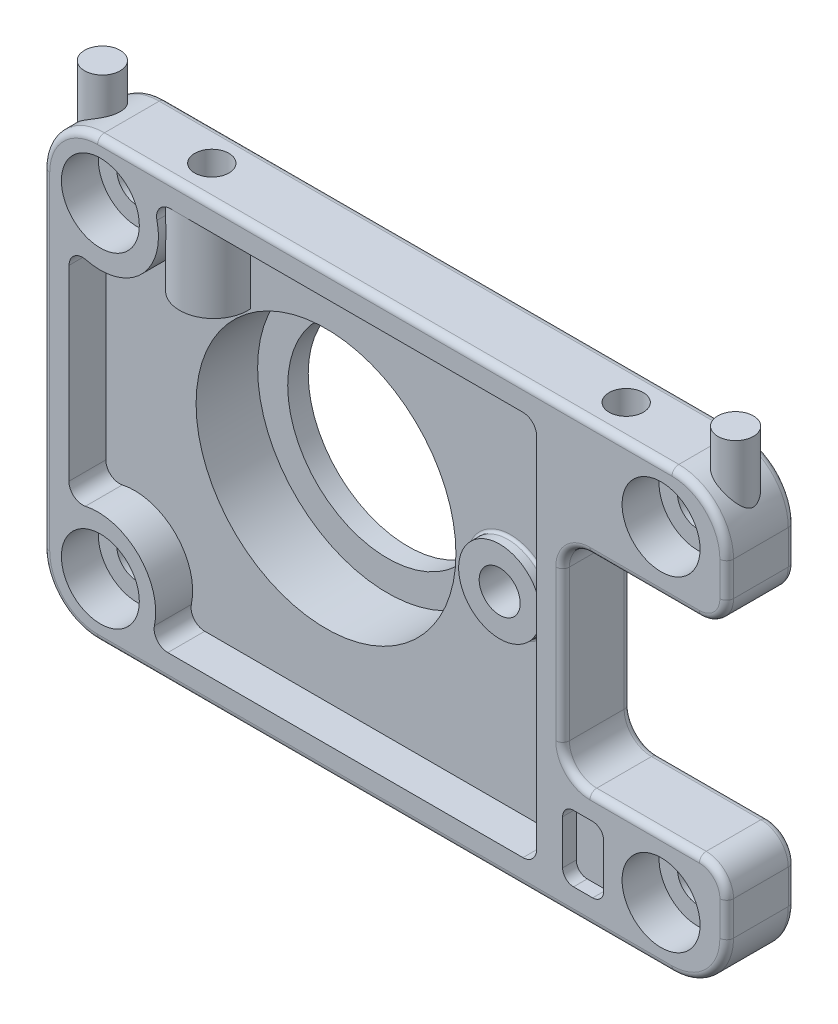
SolidWorks part; units mm, degrees
note: The reader was unsure of these and kept them because the rebuilt part matched: shared geometry of "草图15<3>", "草图16<2>", "草图16<3>".
ref_plane "前视基准面" through (0, 0, 0) normal (0, 0, 1) x (1, 0, 0)
ref_plane "上视基准面" through (0, 0, 0) normal (0, 1, 0) x (1, 0, 0)
ref_plane "右视基准面" through (0, 0, 0) normal (1, 0, 0) x (0, 0, -1)
sketch "草图1" plane through (0, 0, 0) normal (0, 0, 1) x (1, 0, 0)
  line L0 (0, 16) -> (50, 16) construction
  line L1 (0, 0) -> (50, 0)
  line L2 (0, 0) -> (0, 32)
  line L3 (0, 32) -> (50, 32)
  line L4 (50, 0) -> (50, 8.5)
  line L5 (50, 23.5) -> (38, 23.5)
  line L6 (38, 23.5) -> (38, 8.5)
  line L7 (50, 8.5) -> (38, 8.5)
  line L8 (50, 23.5) -> (50, 32)
  line L9 (4.2, 27.9) -> (5.7, 27.9) construction
  line L10 (4.2, 27.9) -> (46.7, 27.9) construction
  line L11 (4.2, 4.1) -> (50, 4.25) construction
  line L12 (25, 0) -> (25, 37.6238) construction
  circle A0 centre (4.2, 27.9) radius 1.5
  circle A1 centre (45.2, 27.9) radius 1.5
  circle A2 centre (45.2, 4.1) radius 1.5
  circle A3 centre (4.2, 4.1) radius 1.5
  circle A4 centre (18, 16) radius 9.5
  point P22 (38, 16)
  dimension "D3" = 3
  dimension "D10" = 18
  dimension "D11" = 19
  dimension "D1" = 50
  dimension "D2" = 32
  dimension "D6" = 4.2
  dimension "D8" = 23.8
  dimension "D12" = 8.5
  dimension "D13" = 12
  dimension "D14" = 41
  dimension "D4" = 2
  dimension "D5" = 2
extrude "凸台-拉伸1" add sketch "草图1" along normal blind 5
sketch "草图2" plane through (0, 0, 5) normal (0, 0, 1) x (1, 0, 0)
  line L0 (38, 8.5) -> (38, 23.5) construction
  line L1 (38, 25.2613) -> (41, 25.2613)
  line L2 (38, 25.2613) -> (38, 30.1)
  line L3 (36.1, 1.9) -> (36.1, 30.1)
  line L4 (7.6949, 1.9) -> (36.1, 1.9)
  line L5 (36.1, 30.1) -> (7.8363, 30.1)
  line L6 (38, 30.1) -> (41, 30.1)
  line L7 (41, 25.2613) -> (41, 30.1)
  line L8 (38, 6.74) -> (38, 1.9)
  line L9 (38, 1.9) -> (41, 1.9)
  line L10 (41, 1.9) -> (41, 6.74)
  line L11 (41, 6.74) -> (38, 6.74)
  line L24 (1.9124, 24.3182) -> (1.9, 7.6949)
  circle A0 centre (4.2, 27.9) radius 1.5 construction
  circle A1 centre (4.2, 27.9) radius 1.5 construction
  circle A2 centre (4.2, 4.1) radius 1.5 construction
  circle A3 centre (4.2, 4.1) radius 1.5 construction
  circle A4 centre (45.2, 27.9) radius 1.5 construction
  circle A5 centre (45.2, 27.9) radius 1.5 construction
  circle A6 centre (45.2, 4.1) radius 1.5 construction
  circle A7 centre (45.2, 4.1) radius 1.5 construction
  circle A8 centre (4.2, 27.9) radius 2.85
  circle A9 centre (4.2, 4.1) radius 2.85
  circle A10 centre (45.2, 4.1) radius 2.85
  circle A11 centre (45.2, 27.9) radius 2.85
  arc A12 (1.9124, 24.3182) -> (7.8363, 30.1) centre (4.2, 27.9) ccw
  circle A15 centre (4.2, 27.9) radius 4.25 construction
  arc A16 (7.6949, 1.9) -> (1.9, 7.6949) centre (4, 4) ccw
  circle M13 centre (45.2, 4.1) radius 1.5
  circle M14 centre (18, 16) radius 9.5
  circle M23 centre (4.2, 27.9) radius 1.5
  circle M24 centre (45.2, 27.9) radius 1.5
  circle M25 centre (4.2, 4.1) radius 1.5
  dimension "D4" = 3
  dimension "D6" = 4.9
  dimension "D1" = 4.8387
  dimension "D7" = 4.84
  dimension "D2" = 1.35
  dimension "D3" = 1.35
  dimension "D5" = 1.4
extrude "切除-拉伸1" cut sketch "草图2" against normal blind 2.7 contours A16 L4 L3 L5 A12 L24 M14 | M14 | A11 M24 | A10 M13 | A8 M23 | A9 M25
fillet "圆角1" radius 1 6 edges at (36.1, 1.9, 3.65) (7.8363, 30.1, 3.65) (1.9124, 24.3182, 3.65) (1.9, 7.6949, 3.65) (7.6949, 1.9, 3.65) (36.1, 30.1, 3.65)
fillet "圆角2" radius 4 4 edges at (0, 0, 2.5) (0, 32, 2.5) (50, 0, 2.5) (50, 32, 2.5)
fillet "圆角3" radius 2 4 edges at (38, 23.5, 2.5) (38, 8.5, 2.5) (50, 8.5, 2.5) (50, 23.5, 2.5)
sketch "草图3" plane through (0, 0, 0) normal (0, 0, -1) x (-1, 0, 0)
  circle A0 centre (-18, 16) radius 11.75
  circle A1 centre (-18, 16) radius 9.5 construction
  circle A2 centre (-18, 16) radius 9.5
  dimension "D1" = 23.5
extrude "凸台-拉伸2" add sketch "草图3" along normal blind 2.2
sketch "草图4" plane through (0, 0, -2.2) normal (0, 0, -1) x (-1, 0, 0)
  circle A0 centre (-18, 16) radius 11.75 construction
  circle A1 centre (-18, 16) radius 11.75
  circle A2 centre (-18, 16) radius 7.3
  dimension "D1" = 14.6
extrude "凸台-拉伸3" add sketch "草图4" along normal blind 1.5
fillet "圆角4" radius 0.5 1 edges at (6.25, 16, -3.7)
fillet "圆角5" radius 0.5 16 edges at (38.5858, 22.9142, 0) (38, 16, 0) (38.5858, 9.0858, 0) (44, 8.5, 0) (49.4142, 7.9142, 0) (50, 5.25, 0) (48.8284, 1.1716, 0) (25, 0, 0) (1.1716, 1.1716, 0) (0, 16, 0) (1.1716, 30.8284, 0) (25, 32, 0) (48.8284, 30.8284, 0) (50, 26.75, 0) (49.4142, 24.0858, 0) (44, 23.5, 0)
ref_plane "基准面1" through (0, -2.5, 0) normal (0, -1, 0) x (-1, 0, 0)
ref_plane "基准面2" through (25, 0, 0) normal (1, 0, 0) x (0, 0, -1)
sketch "草图5" plane through (0, -2.5, 0) normal (0, -1, 0) x (-1, 0, 0)
  line L0 (-50, -2.5) -> (-36.9904, -2.5) construction
  line L2 (-25, -5) -> (-25, 0) construction
  line L3 (-25, 2.2) -> (-25, -2.2) construction
  line L4 (-50, -5) -> (-46, -5) construction
  line L6 (-4, -5) -> (-46, -5) construction
  line L7 (-46, 0) -> (-4, 0) construction
  circle A0 centre (-48, -2.5) radius 1.3
  dimension "D1" = 2.6
  dimension "D3" = 2.5
  dimension "D2" = 23
extrude "凸台-拉伸5" [suppressed] add sketch "草图5" against normal up to surface (3.0359 mm away)
mirror "镜向3" [suppressed] about plane through (25, 0, 0) normal (1, 0, 0)
sketch "草图8" plane through (0, 1.9, 0) normal (0, 1, 0) x (1, 0, 0)
  line L0 (9.1335, -5) -> (35.1, -5) construction
  line L1 (46, 0) -> (4, 0) construction
  line L2 (4, -5) -> (4, -0.5) construction
  line L4 (7.5125, -2.75) -> (12.4875, -2.75)
  line L5 (4, -5) -> (4, -0.5) construction
  line L6 (4, -2.75) -> (14.8659, -2.75) construction
  arc A0 (7.5125, -2.75) -> (12.4875, -2.75) centre (10, -2.5) ccw
  dimension "D1" = 10
extrude "凸台-拉伸6" [suppressed] add sketch "草图8" along normal blind 6
hole_wizard "M3 螺纹孔2" [suppressed] positions "草图10" profile "草图9" tap size "M3" standard "Gb"
sketch "草图10" plane through (0, 0, 0) normal (0, -1, 0) x (-1, 0, 0)
  line L4 (-25, -2.5) -> (-10, -2.5) construction
  line L5 (-25, 0) -> (-25, -5) construction
  line L6 (-4, 0) -> (-46, 0) construction
  line L7 (-46, -5) -> (-4, -5) construction
  point P10 (-10, -2.5)
  point P12 (-40, -2.5)
  dimension "D1" = 30
sketch "草图9" plane through (10, 0, 2.5) normal (1, 0, 0) x (0, 0, -1)
  line L0 (0, 0) -> (0, 6.7511)
  line L1 (0, 6.7511) -> (1.25, 6)
  line L2 (1.25, 6) -> (1.25, 0)
  line L5 (1.25, 0) -> (0, 0)
  line L10 (0, 6.7511) -> (-1.25, 6) construction
  line L11 (0, -6.35) -> (0, 107.95) construction
  dimension "螺纹孔钻头直径" = 2.5
  dimension "螺纹孔钻头深度" = 6
  dimension "导头角度" = 118
cosmetic thread "孔螺蚊线2" [suppressed] parameters "D1"=4, "D2"=3
cosmetic thread "孔螺蚊线3" [suppressed] parameters "D1"=4, "D2"=3
ref_plane "基准面3" through (0, 16, 0) normal (0, -1, 0) x (-1, 0, 0)
sketch "草图11" plane through (0, 32, 0) normal (0, 1, 0) x (1, 0, 0)
  line L2 (12.492, -2.3) -> (7.508, -2.3)
  arc A2 (7.508, -2.3) -> (12.492, -2.3) centre (10, -2.5) ccw
  dimension "D1" = 10
extrude "凸台-拉伸7" add sketch "草图11" against normal blind 8
hole_wizard "M3 螺纹孔3" positions "草图13" profile "草图12" tap size "M3" standard "Gb"
sketch "草图13" plane through (0, 32, 0) normal (0, 1, 0) x (1, 0, 0)
  line L0 (25, -0.5) -> (25, -9.9315) construction
  line L1 (46, -0.5) -> (4, -0.5) construction
  arc A1 (7.358, -2.3) -> (12.342, -2.3) centre (9.85, -2.5) ccw construction
  point P1 (9.85, -2.5)
  point P6 (40.15, -2.5)
  dimension "D1" = 30.3
sketch "草图12" plane through (9.85, 32, 2.5) normal (1, 0, 0) x (0, 0, 1)
  line L0 (0, 0) -> (0, 6.2511)
  line L1 (0, 6.2511) -> (1.25, 5.5)
  line L2 (1.25, 5.5) -> (1.25, 0)
  line L5 (1.25, 0) -> (0, 0)
  line L10 (0, 6.2511) -> (-1.25, 5.5) construction
  line L11 (0, -6.35) -> (0, 107.95) construction
  dimension "螺纹孔钻头直径" = 2.5
  dimension "螺纹孔钻头深度" = 5.5
  dimension "导头角度" = 118
cosmetic thread "孔螺蚊线4" parameters "D1"=4, "D2"=3
cosmetic thread "孔螺蚊线5" parameters "D1"=4, "D2"=3
fillet "圆角6" radius 0.5 16 edges at (1.1716, 1.1716, 5) (0, 16, 5) (1.1716, 30.8284, 5) (25, 32, 5) (48.8284, 30.8284, 5) (50, 26.75, 5) (49.4142, 24.0858, 5) (44, 23.5, 5) (38.5858, 22.9142, 5) (38, 16, 5) (38.5858, 9.0858, 5) (44, 8.5, 5) (49.4142, 7.9142, 5) (50, 5.25, 5) (48.8284, 1.1716, 5) (25, 0, 5)
ref_plane "基准面4" through (0, 34.5, 0) normal (0, 1, 0) x (1, 0, 0)
sketch "草图14" plane through (0, 34.5, 0) normal (0, 1, 0) x (1, 0, 0)
  line L1 (0, -2.5) -> (5.731, -2.5) construction
  line L2 (0, -4.5) -> (0, -0.5) construction
  line L3 (25, -2.2) -> (25, 2.2) construction
  circle A0 centre (1.85, -2.5) radius 1.3
  dimension "D1" = 2.6
  dimension "D2" = 23.15
extrude "凸台-拉伸8" add sketch "草图14" against normal up to surface (3.1269 mm away) up to face at (1.5858, 30.4142, 2.5)
mirror "镜向7" about plane through (25, 0, 0) normal (1, 0, 0) of "凸台-拉伸8"
sketch "草图15" plane through (0, 0, 5) normal (0, 0, 1) x (1, 0, 0)
  line L0 (41, 6.74) -> (38, 6.74) construction
  line L1 (38, 6.74) -> (38, 1.9) construction
  line L2 (38, 1.9) -> (41, 1.9) construction
  line L3 (41, 1.9) -> (41, 6.74) construction
  line L4 (38, 30.1) -> (41, 30.1) construction
  line L5 (38, 25.2613) -> (38, 30.1) construction
  line L6 (38, 25.2613) -> (41, 25.2613) construction
  line L7 (41, 25.2613) -> (41, 30.1) construction
  line L8 (41, 6.74) -> (38, 6.74)
  line L9 (38, 6.74) -> (38, 1.9)
  line L10 (38, 1.9) -> (41, 1.9)
  line L11 (41, 1.9) -> (41, 6.74)
  line L12 (38, 30.1) -> (41, 30.1)
  line L13 (38, 25.2613) -> (38, 30.1)
  line L14 (38, 25.2613) -> (41, 25.2613)
  line L15 (41, 25.2613) -> (41, 30.1)
extrude "切除-拉伸2" [suppressed] cut sketch "草图15" against normal blind 2.5 contours L14 L15 L12 L13
fillet "圆角7" [suppressed] radius 0.8
extrude "切除-拉伸5" cut sketch "草图15<3>" against normal blind 1 contours L10 L11 L8 L9
sketch "草图15<3>" plane through (0, 0, 5) normal (0, 0, 1) x (1, 0, 0) same geometry as "草图15"
fillet "圆角9" radius 0.8 4 edges at (38, 6.74, 4.5) (41, 6.74, 4.5) (41, 1.9, 4.5) (38, 1.9, 4.5)
sketch "草图16" plane through (0, 0, 2.3) normal (0, 0, 1) x (1, 0, 0)
  line L0 (18, 16) -> (41.9863, 16) construction
  circle A0 centre (31.5, 16) radius 3
  circle A1 centre (31.5, 16) radius 1.5
  dimension "D1" = 6
  dimension "D3" = 1.5
  dimension "D2" = 13.5
extrude "凸台-拉伸9" add sketch "草图16" along normal blind 0.8
extrude "凸台-拉伸10" add sketch "草图16<2>" against normal blind 4 contours A0
sketch "草图16<2>" plane through (0, 0, 2.3) normal (0, 0, 1) x (1, 0, 0) same geometry as "草图16"
extrude "切除-拉伸3" cut sketch "草图16<3>" against normal blind 3.6 contours L0 A1 | A1 L0
sketch "草图16<3>" plane through (0, 0, 2.3) normal (0, 0, 1) x (1, 0, 0) same geometry as "草图16"
fillet "圆角8" radius 0.2 2 edges at (34.5, 16, 2.3) (34.5, 16, -1.7)
sketch "草图17" plane through (0, 0, 0) normal (0, 0, -1) x (-1, 0, 0)
  circle A0 centre (-45.2, 27.9) radius 2.85
  circle A1 centre (-4.2, 27.9) radius 2.85
  circle A2 centre (-45.2, 4.1) radius 2.85
  circle A3 centre (-4.2, 4.1) radius 2.85
  circle A4 centre (-45.2, 27.9) radius 1.5 construction
  circle A5 centre (-4.2, 27.9) radius 1.5 construction
  circle A6 centre (-4.2, 4.1) radius 1.5 construction
  circle A7 centre (-45.2, 4.1) radius 1.5 construction
  circle A8 centre (-45.2, 27.9) radius 1.5
  circle A9 centre (-4.2, 27.9) radius 1.5
  circle A10 centre (-4.2, 4.1) radius 1.5
  circle A11 centre (-45.2, 4.1) radius 1.5
  dimension "D1" = 5.7
  dimension "D2" = 5.7
  dimension "D3" = 5.7
  dimension "D4" = 5.7
extrude "切除-拉伸4" cut sketch "草图17" against normal blind 1
